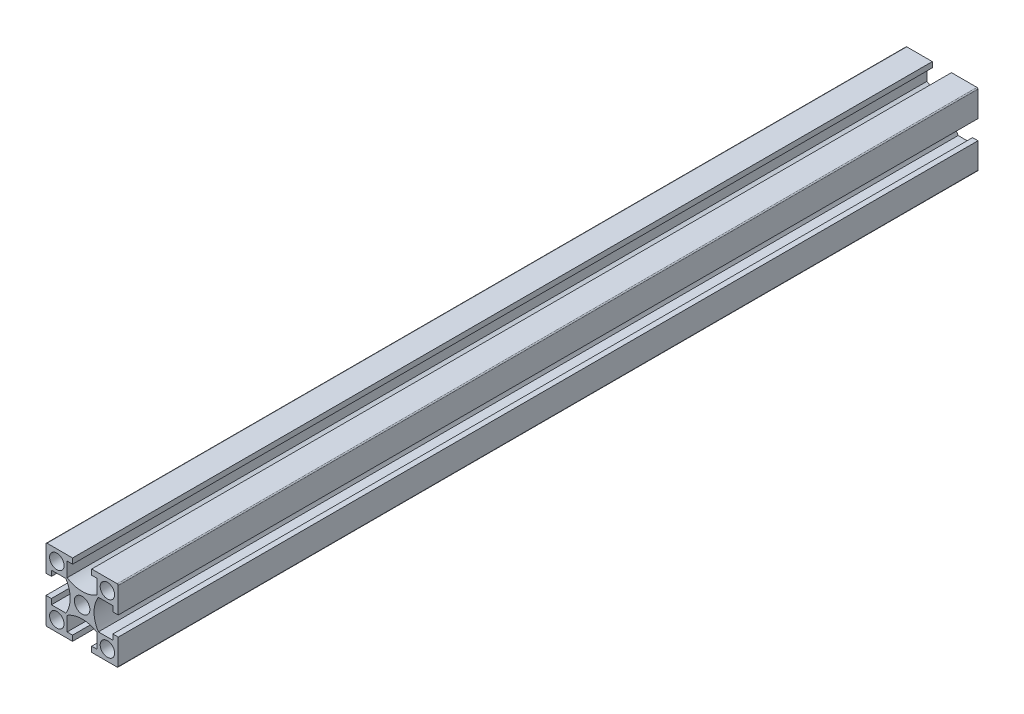
SolidWorks part; units mm, degrees
material "3.0255 (EN-AW 1350A)"
ref_plane "정면" through (0, 0, 0) normal (0, 0, 1) x (1, 0, 0)
ref_plane "윗면" through (0, 0, 0) normal (0, 1, 0) x (1, 0, 0)
ref_plane "우측면" through (0, 0, 0) normal (1, 0, 0) x (0, 0, -1)
sketch "스케치1" plane through (0, 0, 0) normal (0, 0, 1) x (1, 0, 0)
  line L0 (0, 32.0265) -> (0, -31.6588) construction
  line L1 (-10, 10) -> (-10, -10)
  line L2 (-10, 10) -> (10, 10)
  line L3 (-10, 2.65) -> (-8.5, 2.65)
  line L4 (13.6618, 0) -> (-11.6993, 0) construction
  line L5 (-8.5, 2.65) -> (-8.5, 4.15)
  line L6 (-8.5, 4.15) -> (-4.5032, 4.15)
  line L7 (-10, -2.65) -> (-8.5, -2.65)
  line L8 (-8.5, -2.65) -> (-8.5, -4.15)
  line L9 (-8.5, -4.15) -> (-4.5032, -4.15)
  line L10 (-10, -10) -> (10, -10)
  line L11 (10, 10) -> (10, -10)
  circle A0 centre (-7, 7) radius 2
  circle A1 centre (-7, -7) radius 2
  arc A2 (-4.5032, 4.15) -> (-4.5032, -4.15) centre (-11.0587, 0) cw
  circle A3 centre (0, 0) radius 2.15
  circle A4 centre (7, 7) radius 2
  circle A5 centre (7, -7) radius 2
  point P21 (-10, 0)
  point P23 (-3.3, 0)
  point P31 (0, -10)
  point P32 (0, 10)
  dimension "D3" = 4
  dimension "D9" = 6.7
  dimension "D10" = 4.3
  dimension "D11" = 7.7587
  dimension "D1" = 20
  dimension "D2" = 20
  dimension "D4" = 14
  dimension "D5" = 14
  dimension "D6" = 5.3
  dimension "D7" = 8.3
  dimension "D8" = 1.5
extrude "보스-돌출1" add sketch "스케치1" along normal blind 238 contours A0 | A4 | A3 | A5 | A1 | A2 L6 L5 L3 L1 L7 L8 L9 | L2 L11 L10 L1 region at (-6.6069, 0, 0) region at (-7, 7, 0) region at (-7, -7, 0) region at (0, 0, 0) region at (7, 7, 0) region at (7, -7, 0)
extrude "컷-돌출1" cut sketch "스케치1<3>" along normal up to next contours A2 L6 L5 L3 L1 L7 L8 L9 region at (-6.6069, 0, 0)
sketch "스케치1<3>" plane through (0, 0, 0) normal (0, 0, 1) x (1, 0, 0) same geometry as "스케치1"
pattern_circular "원형 패턴1" count 4 over 360 about axis through (0, 0, 238) along (0, 0, -1) of "컷-돌출1" reverse direction yes
fillet "필렛1" radius 0.3 4 edges at (10, -10, 119) (-10, -10, 119) (-10, 10, 119) (10, 10, 119)
sketch "스케치2" plane through (-10, 0, 0) normal (-1, 0, 0) x (0, 0, 1)
  line L0 (0, 4.15) -> (0, -4.15) construction
  line L1 (238, -4.15) -> (238, 4.15) construction
  circle A1 centre (11, 0) radius 2.5
  circle A2 centre (229, 0) radius 2.5
  dimension "D1" = 11
  dimension "D2" = 9
extrude "컷-돌출2" cut sketch "스케치2" against normal through all
sketch "스케치3" plane through (0, 10, 0) normal (0, 1, 0) x (1, 0, 0)
  line L0 (-10, -192) -> (9.7, -192) construction
  line L1 (-10, -238) -> (-10, 0) construction
  line L2 (9.7, -238) -> (9.7, 0) construction
  line L3 (2.65, -238) -> (9.7, -238) construction
  line L4 (-10, -172) -> (9.7, -172) construction
  circle A0 centre (0, -203) radius 2.5
  circle A1 centre (0, -161) radius 2.5
  dimension "D3" = 11
  dimension "D1" = 46
  dimension "D4" = 11
  dimension "D2" = 20
extrude "컷-돌출3" cut sketch "스케치3" against normal through all
